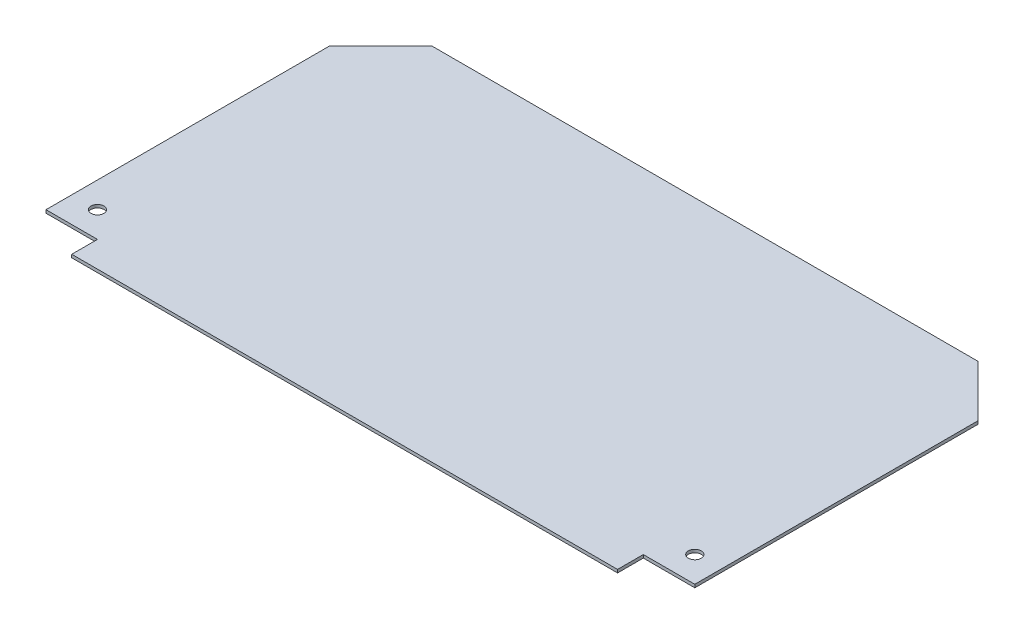
SolidWorks part; units mm, degrees
material "AISI 304"
ref_plane "前基準面" through (0, 0, 0) normal (0, 0, 1) x (1, 0, 0)
ref_plane "上基準面" through (0, 0, 0) normal (0, 1, 0) x (1, 0, 0)
ref_plane "右基準面" through (0, 0, 0) normal (1, 0, 0) x (0, 0, -1)
sketch "草圖1" plane through (0, 0, 0) normal (0, 1, 0) x (1, 0, 0)
  line L0 (-126, 0) -> (-106, 0)
  line L1 (-106, 0) -> (-106, -10)
  line L2 (-106, -10) -> (0, -10)
  line L3 (0, -10) -> (0, 130)
  line L4 (0, 130) -> (-106, 130)
  line L5 (-106, 130) -> (-126, 110)
  line L6 (-126, 110) -> (-126, 0)
  circle A0 centre (-116, 10) radius 2.5
  dimension "D3" = 10
  dimension "D4" = 10
  dimension "D5" = 5
  dimension "D1" = 20
  dimension "D2" = 10
  dimension "D6" = 45
  dimension "D7" = 140
  dimension "D8" = 126
base flange "基材-凸緣1" sketch "草圖1" thickness 1.2 reverse thickness direction no parameters "D1"=0.7366
sketch "草圖3" [suppressed] plane through (0, 0, 0) normal (0, 1, 0) x (1, 0, 0)
  line L1 (-107.5, 130) -> (-107.5, 0)
  line L2 (0, 130) -> (-106, 130) construction
  line L3 (0, -10) -> (0, 130) construction
  line L4 (-126, 0) -> (-106, 0) construction
  dimension "D1" = 107.5
sketch "草圖4" [suppressed] plane through (0, 0, 0) normal (0, 1, 0) x (1, 0, 0)
  line L2 (-106, -3) -> (0, -3)
  line L3 (-106, 0) -> (-106, -10) construction
  line L4 (0, -10) -> (0, 130) construction
  line L5 (-106, -10) -> (0, -10) construction
  dimension "D1" = 7
sketched bend "草圖繪製彎折1" [suppressed] thickness 1.2
bend "草圖繪製彎折2" [suppressed] bend radius 1.8 bend angle 90 parameters "D5"=1
sketch "草圖5" [suppressed] plane through (0, 0, 0) normal (0, 1, 0) x (1, 0, 0)
  line L1 (-104.5, -10) -> (-107.5, -10)
  line L2 (-104.5, -10) -> (-104.5, 0)
  line L3 (-104.5, 0) -> (-107.5, 0)
  line L4 (-107.5, -10) -> (-107.5, 0)
extrude "除料-伸長1" [suppressed] cut sketch "草圖5" along normal through all
sketched bend "草圖繪製彎折3" [suppressed] thickness 1.2
bend "草圖繪製彎折4" [suppressed] bend radius 1.8 bend angle 90 parameters "D5"=2
mirror "鏡射1"
bend "鏡射彎折2" bend radius 1.8 bend angle 90 parameters "D5"=3
sketch "彎折-線1" [suppressed] plane through (0, 0, 0) normal (0, 1, 0) x (1, 0, 0)
sketch "邊界方塊1" [suppressed] plane through (0, 0, 0) normal (0, 1, 0) x (1, 0, 0)
sheet metal parameters "鈑金1" thickness 1.2 parameters "D1"=0.7366
flat pattern "平板-型式1" [suppressed]
sketch "彎折-線2" plane through (0, 0, 0) normal (0, 1, 0) x (1, 0, 0)
  line L0 (-106.385, 129.615) -> (-106.385, 0) construction
  line L1 (-106.385, 129.615) -> (-106.385, 0) construction
sketch3d "邊界方塊2" [suppressed]
  line L0 (-126, 130, 0) -> (-126, -10, 0) construction
  line L1 (0, 130, 0) -> (0, -10, 0) construction
  line L2 (-126, 130, 0) -> (0, 130, 0) construction
  line L3 (-126, -10, 0) -> (0, -10, 0) construction
bend of the flat pattern "平板-<草圖繪製彎折2>2"
sheet metal parameters "鈑金3" thickness 1.2 parameters "D1"=0.7366
flat pattern "平板-型式3"
sketch "彎折-線3" [suppressed] plane through (0, 0, 0) normal (0, 1, 0) x (1, 0, 0)
sketch3d "邊界方塊3" [suppressed]
  line L0 (126, -10, 0) -> (-126, -10, 0) construction
  line L1 (126, 130, 0) -> (-126, 130, 0) construction
  line L2 (126, -10, 0) -> (126, 130, 0) construction
  line L3 (-126, -10, 0) -> (-126, 130, 0) construction
sheet metal parameters "鈑金5" thickness 1.2 parameters "D1"=0.7366
flat pattern "平板-型式1"
sketch "彎折-線2" plane through (0, 0, 0) normal (0, 1, 0) x (1, 0, 0)
  line L0 (-106.385, 129.615) -> (-106.385, 0) construction
  line L1 (-106.385, 129.615) -> (-106.385, 0) construction
  line L2 (-104.5, -1.885) -> (0, -1.885) construction
  line L3 (-104.5, -1.885) -> (0, -1.885) construction
sketch3d "邊界方塊2" [suppressed]
  line L0 (-126, 130, 0) -> (-126, -10, 0) construction
  line L1 (0, 130, 0) -> (0, -10, 0) construction
  line L2 (-126, 130, 0) -> (0, 130, 0) construction
  line L3 (-126, -10, 0) -> (0, -10, 0) construction
bend of the flat pattern "平板-<草圖繪製彎折2>2"
bend of the flat pattern "平板-<草圖繪製彎折4>3"
